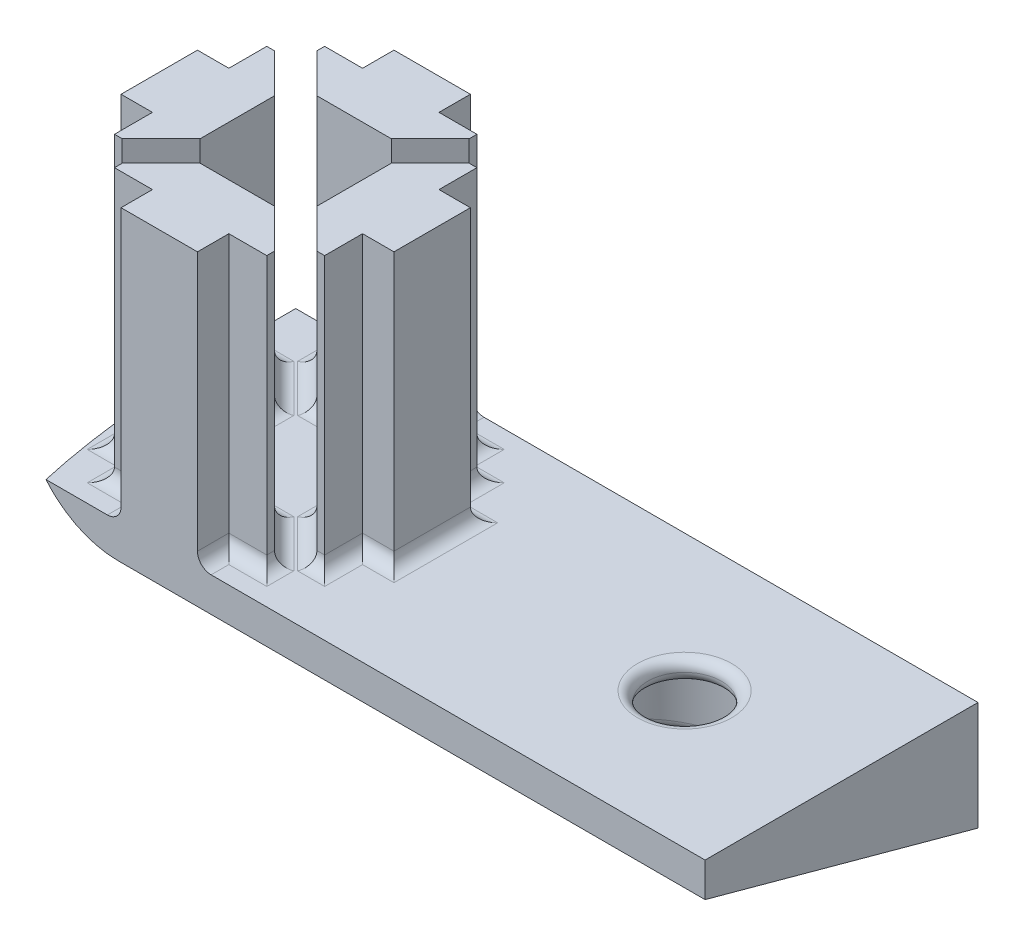
SolidWorks part; units mm, degrees
ref_plane "Front Plane" through (0, 0, 0) normal (0, 0, 1) x (1, 0, 0)
ref_plane "Top Plane" through (0, 0, 0) normal (0, 1, 0) x (1, 0, 0)
ref_plane "Right Plane" through (0, 0, 0) normal (1, 0, 0) x (0, 0, -1)
sketch "Sketch1" plane through (0, 0, 0) normal (0, 1, 0) x (1, 0, 0)
  line L20 (0, 0) -> (50000, 0) construction
  line L21 (-10, -2.8) -> (-10, 49997.2) construction
  line L22 (-10, -2.8) -> (-10, 2.8)
  line L23 (-7.1356, 5.58) -> (-4.28, 2.7244)
  line L24 (-7.7, 5.58) -> (-7.1356, 5.58)
  line L25 (-10, -2.8) -> (-7.7, -2.8)
  line L26 (-4.28, -2.7244) -> (-4.28, 2.7244)
  line L27 (-7.1356, -5.58) -> (-4.28, -2.7244)
  line L28 (-7.7, -5.58) -> (-7.1356, -5.58)
  line L29 (-7.7, -2.8) -> (-7.7, -5.58)
  line L30 (-7.7, 2.8) -> (-7.7, 5.58)
  line L31 (-10, 2.8) -> (-7.7, 2.8)
  line L32 (0, 0) -> (0, -50000) construction
  line L33 (10, 2.8) -> (7.7, 2.8)
  line L34 (7.7, 2.8) -> (7.7, 5.58)
  line L35 (7.7, -2.8) -> (7.7, -5.58)
  line L36 (7.7, -5.58) -> (7.1356, -5.58)
  line L37 (7.1356, -5.58) -> (4.28, -2.7244)
  line L38 (4.28, -2.7244) -> (4.28, 2.7244)
  line L39 (10, -2.8) -> (7.7, -2.8)
  line L40 (7.7, 5.58) -> (7.1356, 5.58)
  line L41 (7.1356, 5.58) -> (4.28, 2.7244)
  line L42 (10, -2.8) -> (10, 2.8)
  line L43 (0, 0) -> (35355.3391, -35355.3391) construction
  line L44 (0, 0) -> (0, -50000) construction
  line L45 (2.8, -10) -> (-2.8, -10)
  line L46 (-5.58, -7.1356) -> (-2.7244, -4.28)
  line L47 (-5.58, -7.7) -> (-5.58, -7.1356)
  line L48 (2.8, -10) -> (2.8, -7.7)
  line L49 (2.7244, -4.28) -> (-2.7244, -4.28)
  line L50 (5.58, -7.1356) -> (2.7244, -4.28)
  line L51 (5.58, -7.7) -> (5.58, -7.1356)
  line L52 (2.8, -7.7) -> (5.58, -7.7)
  line L53 (-2.8, -7.7) -> (-5.58, -7.7)
  line L54 (-2.8, -10) -> (-2.8, -7.7)
  line L55 (-2.8, 10) -> (-2.8, 7.7)
  line L56 (-2.8, 7.7) -> (-5.58, 7.7)
  line L57 (2.8, 7.7) -> (5.58, 7.7)
  line L58 (5.58, 7.7) -> (5.58, 7.1356)
  line L59 (5.58, 7.1356) -> (2.7244, 4.28)
  line L60 (2.7244, 4.28) -> (-2.7244, 4.28)
  line L61 (2.8, 10) -> (2.8, 7.7)
  line L62 (-5.58, 7.7) -> (-5.58, 7.1356)
  line L63 (-5.58, 7.1356) -> (-2.7244, 4.28)
  line L64 (2.8, 10) -> (-2.8, 10)
  point P12 (-4.28, 0)
  point P16 (-10, 0)
  point P28 (10, 0)
  point P29 (4.28, 0)
  point P44 (0, -4.28)
  point P45 (0, -10)
  point P56 (0, 10)
  point P57 (0, 4.28)
  dimension "D1" = 45
extrude "Boss-Extrude1" add sketch "Sketch1" along normal blind 20
sketch "Sketch2" plane through (0, 0, 0) normal (0, -1, 0) x (1, 0, 0)
  line L0 (-10, 10) -> (10, 10)
  line L1 (10, 10) -> (10, -10)
  line L2 (10, -10) -> (-10, -10)
  line L3 (-10, -10) -> (-10, 10)
  line L4 (2.8, -10) -> (-2.8, -10) construction
  line L5 (10, 2.8) -> (10, -2.8) construction
  line L6 (-2.8, 10) -> (2.8, 10) construction
  line L7 (-10, -2.8) -> (-10, 2.8) construction
extrude "Boss-Extrude2" add sketch "Sketch2" along normal blind 20
sketch "Sketch3" plane through (10, 0, 0) normal (1, 0, 0) x (0, 0, -1)
  line L2 (10.5967, -8.1372) -> (10.5967, -38.3455)
  line L3 (10.5967, -38.3455) -> (-10.4111, -38.3455)
  line L4 (-10.4111, -38.3455) -> (-10.4111, -2.4027)
  line L5 (10.5967, -8.1372) -> (-10.4111, -2.4027)
extrude "Cut-Extrude1" cut sketch "Sketch3" against normal through all
sketch "Sketch4" plane through (10, 0, 0) normal (1, 0, 0) x (0, 0, -1)
  line L0 (10, -7.9743) -> (10, 0)
  line L1 (10, 0) -> (-10, 0)
  line L2 (-10, 0) -> (-10, -2.5149)
  line L3 (-10, -2.5149) -> (10, -7.9743)
extrude "Boss-Extrude3" add sketch "Sketch4" along normal blind 30
sketch "Sketch5" plane through (0, 0, 0) normal (0, 1, 0) x (1, 0, 0)
  line L0 (40, 10) -> (40, -10) construction
  line L1 (0, 0) -> (-50000, 0) construction
  circle A0 centre (28.5, 0) radius 2.7
  point P4 (40, 0)
  dimension "D2" = 5.4
  dimension "D1" = 11.5
extrude "Cut-Extrude2" cut sketch "Sketch5" against normal blind 30
ref_plane "Plane1" through (0, -1.5, 0) normal (0, 1, 0) x (1, 0, 0)
sketch "Sketch6" plane through (0, -1.5, 0) normal (0, 1, 0) x (1, 0, 0)
  circle A0 centre (28.5, 0) radius 5
  dimension "D1" = 10
extrude "Cut-Extrude3" cut sketch "Sketch6" against normal blind 30
fillet "Fillet1" radius 7 1 edges at (-10, -5.2446, 0)
fillet "Fillet3" radius 1 37 edges at (4.1522, 0, -5.7078) (5.58, 0, -7.4178) (4.19, 0, -7.7) (2.8, 0, -8.85) (-2.8, 0, -8.85) (-4.19, 0, -7.7) (-5.58, 0, -7.4178) (-4.1522, 0, -5.7078) (0, 0, -4.28) (4.28, 0, 0) (5.7078, 0, -4.1522) (7.4178, 0, -5.58) (7.7, 0, -4.19) (8.85, 0, -2.8) (10, 0, 0) (8.85, 0, 2.8) (7.7, 0, 4.19) (5.7078, 0, 4.1522) (7.4178, 0, 5.58) (2.8, 0, 8.85) (4.19, 0, 7.7) (5.58, 0, 7.4178) (4.1522, 0, 5.7078) (0, 0, 4.28) (-4.1522, 0, 5.7078) (-5.58, 0, 7.4178) (-2.8, 0, 8.85) (-4.19, 0, 7.7) (-8.5838, 0, 2.8) (-7.7, 0, 4.19) (-7.4178, 0, 5.58) (-5.7078, 0, 4.1522) (-4.28, 0, 0) (-5.7078, 0, -4.1522) (-7.4178, 0, -5.58) (-7.7, 0, -4.19) (-8.7979, 0, -2.8)
fillet "Fillet4" radius 0.75 4 edges at (28.5, -3.8798, 5) (28.5, -1.5, 5) (28.5, 0, 2.7) (28.5, -1.5, 2.7)
